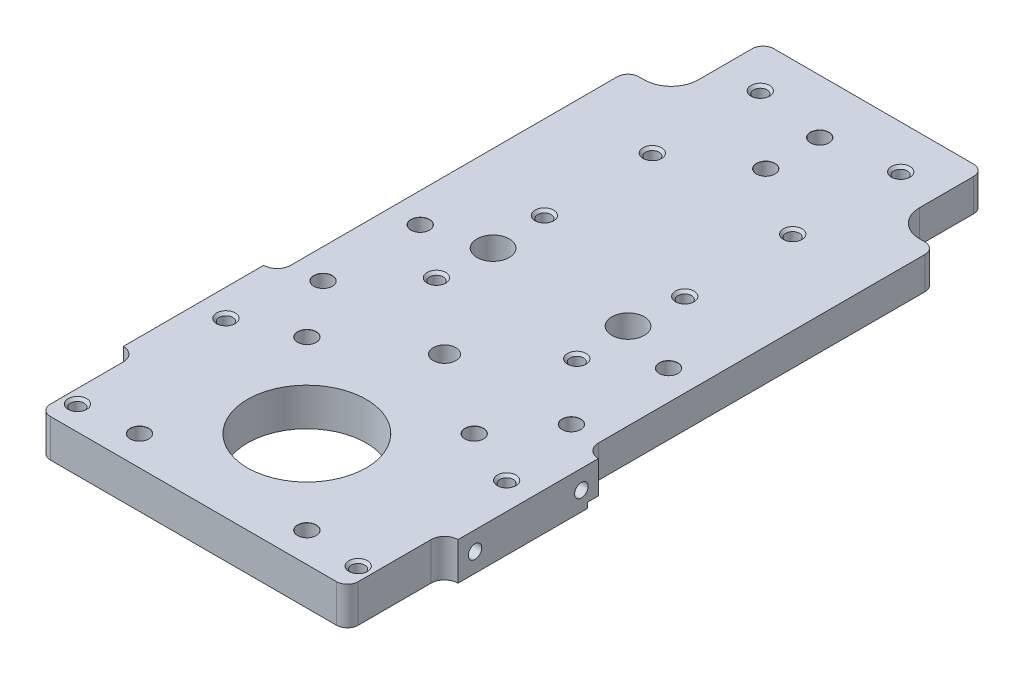
SolidWorks part; units mm, degrees
ref_plane "Top" through (0, 0, 0) normal (0, 0, 1) x (1, 0, 0)
ref_plane "Front" through (0, 0, 0) normal (0, 1, 0) x (1, 0, 0)
ref_plane "Right" through (0, 0, 0) normal (1, 0, 0) x (0, 0, -1)
ref_plane "Left Plane" through (-31, 0, 0) normal (1, 0, 0) x (0, 0, -1)
sketch "Plate Main Sketch" plane through (-158.0855, 0, 24.6791) normal (0, 1, 0) x (-1, 0, 0)
  line L1 (-178.5855, -24.6791) -> (-137.5855, -24.6791)
  line L2 (-127.0855, 57.3209) -> (-127.0855, 83.3209)
  line L3 (-129.5855, 101.3209) -> (-186.5855, 101.3209)
  line L4 (-129.5855, 101.3209) -> (-129.5855, 85.8209)
  line L5 (-158.0855, 101.3209) -> (-158.0855, -24.6791) construction
  line L6 (-178.5855, -12.6791) -> (-178.5855, -24.6791)
  line L7 (-129.5855, 54.8209) -> (-129.5855, -7.6791)
  line L8 (-129.5855, -7.6791) -> (-132.5855, -7.6791)
  line L9 (-137.5855, -12.6791) -> (-137.5855, -24.6791)
  line L10 (-186.5855, -7.6791) -> (-183.5855, -7.6791)
  line L11 (-186.5855, 54.8209) -> (-186.5855, -7.6791)
  line L12 (-189.0855, 57.3209) -> (-189.0855, 83.3209)
  line L13 (-186.5855, 101.3209) -> (-186.5855, 85.8209)
  arc A0 (-129.5855, 85.8209) -> (-127.0855, 83.3209) centre (-127.0855, 85.8209) ccw
  arc A1 (-129.5855, 54.8209) -> (-127.0855, 57.3209) centre (-127.0855, 54.8209) cw
  arc A2 (-132.5855, -7.6791) -> (-137.5855, -12.6791) centre (-132.5855, -12.6791) ccw
  arc A3 (-183.5855, -7.6791) -> (-178.5855, -12.6791) centre (-183.5855, -12.6791) cw
  arc A4 (-186.5855, 54.8209) -> (-189.0855, 57.3209) centre (-189.0855, 54.8209) ccw
  arc A5 (-186.5855, 85.8209) -> (-189.0855, 83.3209) centre (-189.0855, 85.8209) cw
  circle A18 centre (-158.0855, 80.3209) radius 11
  circle A20 centre (-145.5855, 33.3209) radius 3
  circle A21 centre (-170.5855, 33.3209) radius 3
  dimension "D2" = 5
  dimension "D8" = 22
  dimension "D9" = 6
  dimension "D1" = 2.5
  dimension "D3" = 62
  dimension "D4" = 126
  dimension "D5" = 18
  dimension "D6" = 44
  dimension "D15" = 21
  dimension "D17" = 8
  dimension "D7" = 109
  dimension "D10" = 58
  dimension "D11" = 16
extrude "Extrude Plate Main" add sketch "Plate Main Sketch" along normal blind 7
fillet "Corner Fillets" radius 2 6 edges at (-28.5, 3.5, 126) (-28.5, 3.5, 17) (-20.5, 3.5, 0) (20.5, 3.5, 0) (28.5, 3.5, 17) (28.5, 3.5, 126)
sketch "Reccess Sketch" plane through (0, 0, 0) normal (0, 1, 0) x (1, 0, 0)
  line L0 (-8.25, 0) -> (-8.25, -81)
  line L1 (-11.25, -84) -> (-31, -84)
  line L2 (-31, -84) -> (-31, 0)
  line L3 (-31, 0) -> (-8.25, 0)
  line L4 (0, 0) -> (0, -84) construction
  line L5 (31, 0) -> (8.25, 0)
  line L6 (8.25, 0) -> (8.25, -81)
  line L7 (31, -84) -> (31, 0)
  line L8 (11.25, -84) -> (31, -84)
  arc A0 (-8.25, -81) -> (-11.25, -84) centre (-11.25, -81) cw
  arc A1 (8.25, -81) -> (11.25, -84) centre (11.25, -81) ccw
  point P7 (-8.25, -84)
  dimension "D4" = 3
  dimension "D1" = 84
  dimension "D2" = 31
  dimension "D3" = 22.75
hole_wizard "M3x0.5 Tapped Holes" positions "Sketch12" profile "Sketch13" tap size "M3x0.5" standard "ANSI Metric" end condition through all
sketch "Sketch12" plane through (0, 0, 0) normal (0, -1, 0) x (-1, 0, 0)
  line L0 (-13, -8) -> (-13, -68) construction
  line L2 (13, -68) -> (13, -8) construction
  line L4 (26, -121.5) -> (-26, -121.5) construction
  line L5 (-26, -121.5) -> (-26, -94) construction
  line L6 (-26, -94) -> (26, -94) construction
  line L7 (26, -94) -> (26, -121.5) construction
  line L11 (31, -126) -> (-31, -126) construction
  line L12 (31, -126) -> (31, 0) construction
  line L13 (31, 0) -> (-31, 0) construction
  line L14 (-31, -126) -> (-31, 0) construction
  line L15 (0, 0) -> (0, -126) construction
  line L16 (31, -63) -> (-31, -63) construction
  point P0 (-26, -121.5)
  point P2 (-26, -94)
  point P4 (26, -94)
  point P8 (13, -68)
  point P10 (13, -48)
  point P12 (13, -28)
  point P14 (13, -8)
  point P16 (-13, -8)
  point P18 (-13, -28)
  point P20 (-13, -48)
  point P22 (-13, -68)
  point P477 (26, -121.5)
  dimension "D1" = 126
  dimension "D2" = 62
  dimension "D3" = 118
  dimension "D4" = 98
  dimension "D5" = 78
  dimension "D6" = 58
  dimension "D7" = 18
  dimension "D8" = 18
  dimension "D9" = 5
  dimension "D10" = 5
  dimension "D11" = 4.5
  dimension "D12" = 32
sketch "Sketch13" plane through (26, 0, 121.5) normal (1, 0, 0) x (0, 0, -1)
  line L0 (0, 0) -> (0, 7)
  line L1 (0, 7) -> (1.725, 7)
  line L2 (1.25, 6.525) -> (1.25, 0)
  line L5 (1.25, 0) -> (0, 0)
  line L7 (1.725, 7) -> (1.25, 6.525)
  line L8 (-1.725, 7) -> (-1.25, 6.525) construction
  line L11 (0, -6.35) -> (0, 107.95) construction
  dimension "Thru Tap Drill Dia." = 2.5
  dimension "Thru Tap Drill Depth" = 7
  dimension "Far C'Sink Dia." = 3.45
  dimension "Far C'Sink Angle" = 90
cosmetic thread "Hole Thread54" parameters "D2"=3
cosmetic thread "Hole Thread55" parameters "D2"=3
cosmetic thread "Hole Thread56" parameters "D2"=3
cosmetic thread "Hole Thread57" parameters "D2"=3
cosmetic thread "Hole Thread58" parameters "D2"=3
cosmetic thread "Hole Thread59" parameters "D2"=3
cosmetic thread "Hole Thread60" parameters "D2"=3
cosmetic thread "Hole Thread61" parameters "D2"=3
cosmetic thread "Hole Thread62" parameters "D2"=3
cosmetic thread "Hole Thread63" parameters "D2"=3
cosmetic thread "Hole Thread64" parameters "D2"=3
cosmetic thread "Hole Thread65" parameters "D2"=3
hole_wizard "M3 Counter Bores" positions "Sketch4" profile "Sketch5" counterbore size "M3" standard "ANSI Metric" end condition through all
sketch "Sketch4" plane through (0, 0, 0) normal (0, -1, 0) x (-1, 0, 0)
  line L0 (31, -126) -> (-31, -126) construction
  line L1 (-31, -126) -> (-31, 0) construction
  line L2 (-31, 0) -> (31, 0) construction
  line L3 (31, 0) -> (31, -126) construction
  line L5 (15.5, -120.5) -> (-15.5, -120.5) construction
  line L6 (-15.5, -120.5) -> (-15.5, -89.5) construction
  line L7 (-15.5, -89.5) -> (15.5, -89.5) construction
  line L8 (15.5, -89.5) -> (15.5, -120.5) construction
  line L10 (0, -126) -> (0, 0) construction
  point P0 (15.5, -120.5)
  point P3 (-15.5, -120.5)
  point P6 (-15.5, -89.5)
  point P9 (15.5, -89.5)
  point P12 (23, -79)
  point P15 (-23, -79)
  point P18 (-23, -61)
  point P21 (23, -61)
  point P24 (0, -20)
  point P27 (0, -10)
  point P42 (0, 0)
  point P65 (0, -120.5)
  dimension "D1" = 126
  dimension "D2" = 62
  dimension "D3" = 31
  dimension "D4" = 31
  dimension "D5" = 5.5
  dimension "D6" = 47
  dimension "D7" = 65
  dimension "D8" = 106
  dimension "D9" = 116
  dimension "D10" = 8
  dimension "D11" = 8
sketch "Sketch5" plane through (-15.5, 0, 120.5) normal (1, 0, 0) x (0, 0, -1)
  line L0 (0, 0) -> (0, 7)
  line L1 (1.7, 6.975) -> (1.725, 7)
  line L2 (1.7, 6.975) -> (1.7, 4.5)
  line L3 (1.7, 4.5) -> (3, 4.5)
  line L4 (3, 4.5) -> (3, 0)
  line L5 (3, 0) -> (0, 0)
  line L11 (0, -6.35) -> (0, 107.95) construction
  line L12 (1.725, 7) -> (0, 7)
  line L13 (-1.7, 6.975) -> (-1.725, 7) construction
  dimension "Thru Hole Dia." = 3.4
  dimension "Thru Hole Depth" = 7
  dimension "C'Bore Dia." = 6
  dimension "C'Bore Depth" = 4.5
  dimension "Far C'Sink Dia." = 3.45
  dimension "Far C'Sink Angle" = 90
hole_wizard "M5x0.8 Tapped Hole1" positions "Sketch14" profile "Sketch15" tap size "M5x0.8" standard "ANSI Metric" end condition through all
sketch "Sketch14" plane through (0, 0, 0) normal (0, -1, 0) x (-1, 0, 0)
  point P0 (0, -79.5)
  dimension "D1" = 79.5
sketch "Sketch15" plane through (0, 0, 79.5) normal (1, 0, 0) x (0, 0, -1)
  line L0 (0, 0) -> (0, 7)
  line L1 (0, 7) -> (2.1, 7)
  line L2 (2.1, 7) -> (2.1, 0)
  line L5 (2.1, 0) -> (0, 0)
  line L11 (0, -6.35) -> (0, 107.95) construction
  dimension "Thru Tap Drill Dia." = 4.2
  dimension "Thru Tap Drill Depth" = 7
cosmetic thread "Hole Thread66" parameters "D2"=5
extrude "Cut Recess" cut sketch "Reccess Sketch" along normal blind 1
hole_wizard "Left Z-Axis Sensors M3x0.5 Tapped Holes" positions "Sketch16" profile "Sketch17" tap size "M3x0.5" standard "ANSI Metric"
sketch "Sketch16" plane through (-31, 0, 0) normal (1, 0, 0) x (0, 0, -1)
  line L0 (0, 0) -> (-126, 0) construction
  line L2 (-108, 0) -> (-108, 7) construction
  line L4 (-82, 0) -> (-82, 7) construction
  line L6 (-108, 7) -> (-82, 7) construction
  line L8 (-108, 3.5) -> (-82, 3.5) construction
  line L10 (-95, 3.5) -> (-95, 0) construction
  point P0 (-85.15, 3.5)
  point P2 (-104.85, 3.5)
  dimension "D1" = 126
  dimension "D2" = 7
  dimension "D3" = 18
  dimension "D4" = 44
  dimension "D5" = 9.85
  dimension "D6" = 9.85
sketch "Sketch17" plane through (-31, 3.5, 85.15) normal (0, 1, 0) x (0, 0, 1)
  line L0 (0, 0) -> (0, 10.7511)
  line L1 (0, 10.7511) -> (1.25, 10)
  line L2 (1.25, 10) -> (1.25, 0)
  line L5 (1.25, 0) -> (0, 0)
  line L10 (0, 10.7511) -> (-1.25, 10) construction
  line L11 (0, -6.35) -> (0, 107.95) construction
  dimension "Tap Drill Dia." = 2.5
  dimension "Tap Drill Depth" = 10
  dimension "Drill Angle" = 118
cosmetic thread "Hole Thread67" parameters "D1"=7, "D2"=3
cosmetic thread "Hole Thread68" parameters "D1"=7, "D2"=3
mirror "Right Z-Axis Sensor Holes Mirror" about plane through (0, 0, 0) normal (1, 0, 0) of "Left Z-Axis Sensors M3x0.5 Tapped Holes"
cosmetic thread "Hole Thread69" parameters "D1"=7, "D2"=3
cosmetic thread "Hole Thread70" parameters "D1"=7, "D2"=3
equation "\"M5 Tap Hole 75%\"= 4.2"
equation "\"Bracket Width\"= 62mm"
equation "\"D3@Plate Main Sketch\"=\"Bracket Width\""
equation "\"Bracket Height\"= 126mm"
equation "\"D4@Plate Main Sketch\"=\"Bracket Height\""
equation "\"D1@Sketch4\"=\"Bracket Height\""
equation "\"D2@Sketch4\"=\"Bracket Width\""
equation "\"D1@Sketch12\"=\"Bracket Height\""
equation "\"D2@Sketch12\"=\"Bracket Width\""
equation "\"D2@Reccess Sketch\" = 0.5 * \"Bracket Width\""
equation "\"D1@Left Plane\" = \"Bracket Width\" / 2"
equation "\"D1@Sketch16\"=\"Bracket Height\""
equation "\"D2@Sketch16\"=\"Bracket Thickness\""
equation "\"Bracket Thickness\"= 7mm"
equation "\"Thickness@Extrude Plate Main\"=\"Bracket Thickness\""
